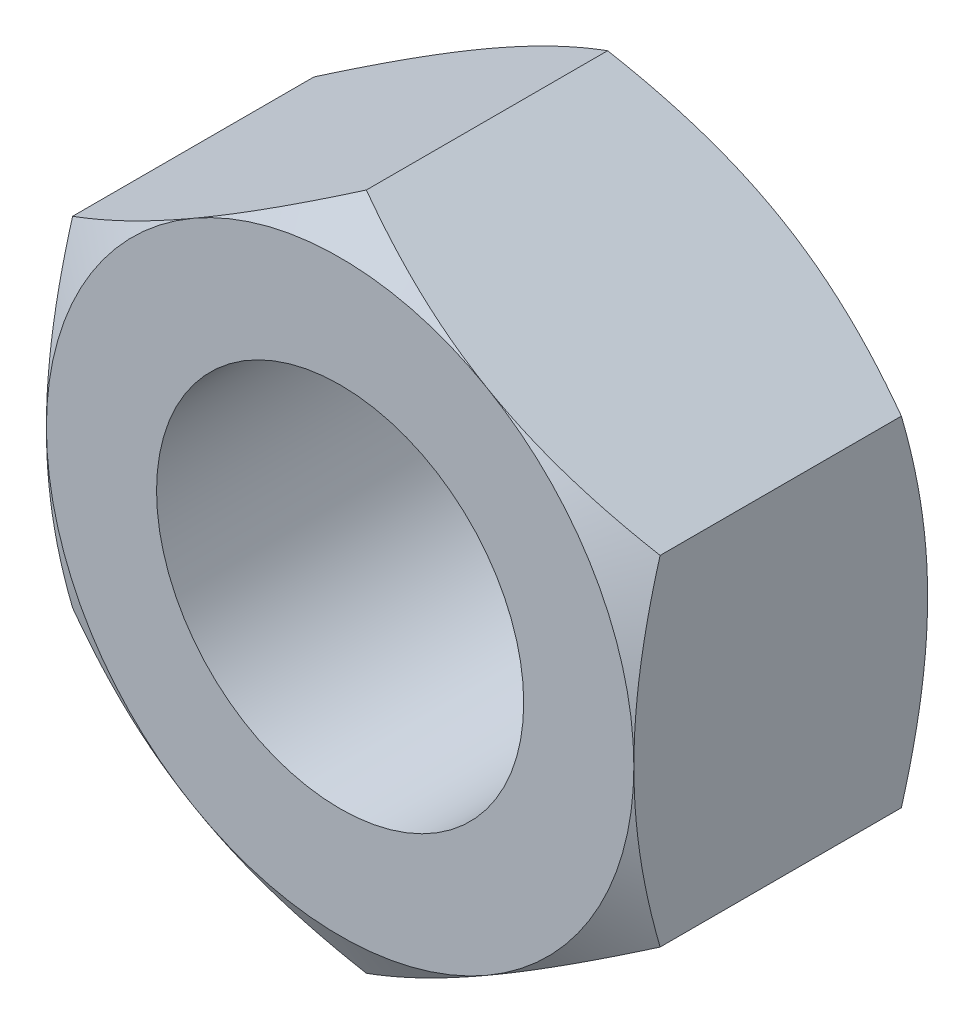
SolidWorks part; units mm, degrees
ref_plane "Plan1" through (0, 0, 0) normal (0, 0, 1) x (1, 0, 0)
ref_plane "Plan2" through (0, 0, 0) normal (0, 1, 0) x (1, 0, 0)
ref_plane "Plan3" through (0, 0, 0) normal (1, 0, 0) x (0, 0, -1)
sketch "Esquisse1" plane through (0, 0, 0) normal (0, 0, 1) x (1, 0, 0)
  line L0 (0, 0) -> (8, 0) construction
  line L1 (8, -4.6188) -> (8, 4.6188)
  line L2 (0, 0) -> (8, 4.6188) construction
  line L3 (0, 0) -> (0, 9.2376) construction
  line L4 (8, 4.6188) -> (0, 9.2376)
  line L5 (8, -4.6188) -> (0, -9.2376)
  line L6 (-8, -4.6188) -> (0, -9.2376)
  line L7 (-8, -4.6188) -> (-8, 4.6188)
  line L8 (-8, 4.6188) -> (0, 9.2376)
  circle A0 centre (0, 0) radius 8 construction
  circle A1 centre (0, 0) radius 9.2376 construction
  dimension "D2" = 16
  dimension "D1" = 30
extrude "Base-Extrusion" add sketch "Esquisse1" against normal blind 8
sketch "Esquisse2" plane through (0, 0, 0) normal (0, 1, 0) x (1, 0, 0)
  line L0 (-8, 0) -> (-15.9282, 0)
  line L1 (0, 8) -> (0, 0) construction
  line L2 (-8, 8) -> (-15.9282, 8)
  line L3 (-15.9282, 8) -> (-15.9282, 0)
  line L5 (-14.9282, 4) -> (-8, 8)
  line L6 (0, 8) -> (0, 0) construction
  line L7 (-8, 0) -> (-14.9282, 4)
  dimension "D1" = 30
  dimension "D2" = 1
  dimension "D3" = 30
revolve "Enlèvement de matière-Révolution1" cut sketch "Esquisse2" angle 360 about L6
sketch "Esquisse3" plane through (0, 0, 0) normal (0, 0, 1) x (1, 0, 0)
  circle A0 centre (0, 0) radius 5
  dimension "D1" = 10
extrude "Enlèv. mat.-Extru.1" cut sketch "Esquisse3" against normal through all
ref_axis "Axe1" through (0, 0, -50) along (0, 0, 1)
